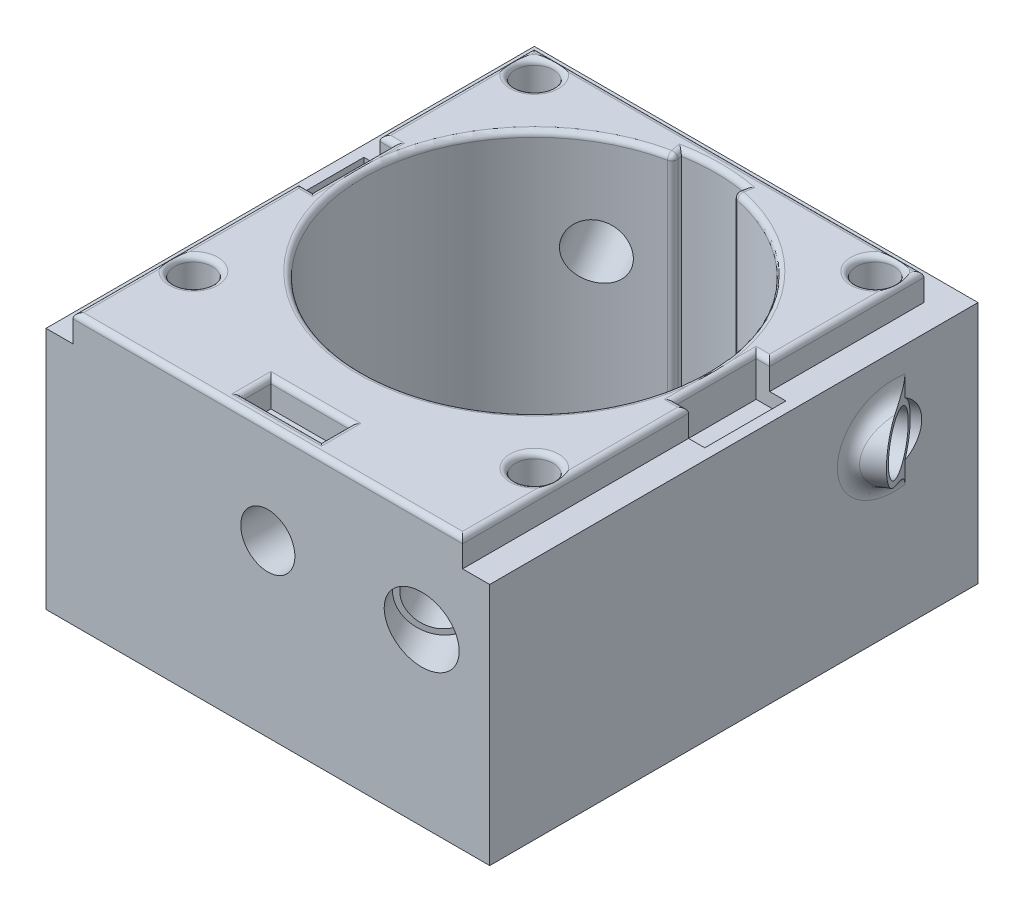
SolidWorks part; units mm, degrees
note: '?' marks a value the reader was unsure of.
ref_plane "Front Plane" through (0, 0, 0) normal (0, 0, 1) x (1, 0, 0)
ref_plane "Top Plane" through (0, 0, 0) normal (0, 1, 0) x (1, 0, 0)
ref_plane "Right Plane" through (0, 0, 0) normal (1, 0, 0) x (0, 0, -1)
sketch "Sketch1" plane through (0, 0, 0) normal (0, 1, 0) x (1, 0, 0)
  line L1 (-20.828, 22.9235) -> (20.828, 22.9235)
  line L2 (-20.828, 22.9235) -> (-20.828, -22.9235)
  line L3 (-20.828, -22.9235) -> (20.828, -22.9235)
  line L4 (20.828, 22.9235) -> (20.828, -22.9235)
  line L5 (-20.828, 22.9235) -> (20.828, -22.9235) construction
  line L6 (-20.828, -22.9235) -> (20.828, 22.9235) construction
  point P0 (0, 0)
  dimension "D1" = 45.847
  dimension "D2" = 41.656
extrude "Boss-Extrude1" add sketch "Sketch1" along normal blind 25.4 contours L2 L1 L4 L3
sketch "Sketch2" plane through (0, 25.4, 0) normal (0, 1, 0) x (1, 0, 0)
  line L0 (0, 22.9235) -> (0, 2.0955) construction
  line L1 (-20.828, 22.9235) -> (20.828, 22.9235) construction
  circle A0 centre (0, 2.0955) radius 16.129
  dimension "D2" = 32.258
  dimension "D1" = 20.828
ref_axis "Axis1" through (0, 25.4, -2.0955) along (0, 1, 0)?
sketch "Sketch7" plane through (0, 0, 22.9235) normal (0, 0, 1) x (1, 0, 0)
  line L0 (0, 0) -> (0, 16.002) construction
  line L1 (-20.828, 0) -> (20.828, 0) construction
  circle A0 centre (0, 16.002) radius 3.048
  dimension "D2" = 6.096
  dimension "D1" = 16.002
extrude "Boss-Extrude5" add sketch "Sketch7" along normal blind 23.114 separate body
sketch "Sketch25" plane through (0, 0, 22.9235) normal (0, 0, -1) x (-1, 0, 0)
  circle A0 centre (0, 16.002) radius 3.048 construction
  circle A1 centre (0, 16.002) radius 3.048 construction
  circle A2 centre (0, 16.002) radius 2.54
  dimension "D1" = 0.508
extrude "Boss-Extrude6" add sketch "Sketch25" along normal blind 14.478
pattern_circular "CirPattern2" count 2 every 120 about axis through (0, 25.4, -2.0955) along (0, 1, 0) of bodies 125
pattern_circular "CirPattern3" count 2 over 360 about axis through (0, 25.4, -2.0955) along (0, 1, 0)
pattern_circular "CirPattern4" count 2 every 30 about axis through (0, 25.4, -2.0955) along (0, 1, 0) of bodies 125
combine bodies "Combine1" bodies to combine 101 125 129 127 128
sketch "Sketch30" plane through (22.5745, 0, -13.0334) normal (0.866, 0, -0.5) x (-0.5, 0, -0.866)
  line L2 (3.4929, 18.5464) -> (3.4929, 17.9087)
  line L3 (3.4929, 14.0953) -> (3.4929, 13.4576)
  line L4 (3.4929, 18.5464) -> (3.4929, 17.9087) construction
  line L5 (3.4929, 14.0953) -> (3.4929, 13.4576) construction
  circle A0 centre (1.8148, 16.002) radius 2.54
  circle A1 centre (1.8148, 16.002) radius 3.048
  arc A2 (3.4929, 13.4576) -> (3.4929, 18.5464) centre (1.8148, 16.002) ccw
  arc A3 (3.4929, 14.0953) -> (3.4929, 17.9087) centre (1.8148, 16.002) ccw
  arc A4 (3.4929, 13.4576) -> (3.4929, 18.5464) centre (1.8148, 16.002) ccw construction
  arc A5 (3.4929, 14.0953) -> (3.4929, 17.9087) centre (1.8148, 16.002) ccw construction
  point P5 (0, 0)
  dimension "D1" = 0
extrude "Boss-Extrude8" add sketch "Sketch30" against normal blind 3.81 contours A1 | A0
sketch "Sketch31" plane through (-13.4169, 0, -23.2387) normal (-0.5, 0, -0.866) x (-0.866, 0, 0.5)
  circle A0 centre (-1.0478, 16.002) radius 2.54 construction
  circle A1 centre (-1.0478, 16.002) radius 2.54
  circle A2 centre (-1.0478, 16.002) radius 3.048
extrude "Boss-Extrude9" add sketch "Sketch31" against normal blind 3.302
extrude "Cut-Extrude1" cut sketch "Sketch2" against normal up to surface (25.4 mm away) up to face at (0, 0, 0)
sketch "Sketch3" plane through (0, 25.4, 0) normal (0, 1, 0) x (1, 0, 0)
  line L0 (-18.415, 2.0955) -> (18.415, 2.0955) construction
  line L1 (0, 2.0955) -> (0, -22.9235) construction
  line L2 (17.018, -1.7145) -> (19.812, -1.7145)
  line L3 (17.018, -1.7145) -> (17.018, 5.9055)
  line L4 (17.018, 5.9055) -> (19.812, 5.9055)
  line L5 (19.812, -1.7145) -> (19.812, 5.9055)
  line L6 (17.018, -1.7145) -> (19.812, 5.9055) construction
  line L7 (17.018, 5.9055) -> (19.812, -1.7145) construction
  line L9 (-17.018, 5.9055) -> (-19.812, -1.7145) construction
  line L10 (-17.018, -1.7145) -> (-19.812, 5.9055) construction
  line L11 (-19.812, -1.7145) -> (-19.812, 5.9055)
  line L12 (-17.018, 5.9055) -> (-19.812, 5.9055)
  line L13 (-17.018, -1.7145) -> (-17.018, 5.9055)
  line L14 (-17.018, -1.7145) -> (-19.812, -1.7145)
  point P14 (0, 2.0955)
  dimension "D1" = 18.415
  dimension "D2" = 7.62
  dimension "D3" = 2.794
extrude "Cut-Extrude2" cut sketch "Sketch3" against normal blind 3.81
sketch "Sketch6" plane through (0, 25.4, 0) normal (0, 1, 0) x (1, 0, 0)
  line L0 (0, 2.0955) -> (0, 18.2245) construction
  line L1 (0, 2.0955) -> (-2.9551, 18.855)
  line L2 (0, 2.0955) -> (2.9551, 18.855)
  circle A0 centre (0, 2.0955) radius 17.018
  circle A1 centre (0, 2.0955) radius 16.129 construction
  circle M16 centre (0, 2.0955) radius 16.129
  dimension "D1" = 34.036
  dimension "D2" = 10
extrude "Cut-Extrude6" cut sketch "Sketch6" against normal up to surface (25.4 mm away) contours L2 A0 L1 M16 | L0 L2 M16 | L1 L0 M16
sketch "Sketch14" plane through (0, 25.4, 0) normal (0, 1, 0) x (1, 0, 0)
  line L0 (20.828, 22.9235) -> (20.828, -22.9235) construction
  line L1 (-20.828, 22.9235) -> (20.828, 22.9235)
  line L2 (-20.828, 22.9235) -> (-20.828, 20.3835)
  line L3 (-20.828, 20.3835) -> (20.828, 20.3835)
  line L4 (20.828, 22.9235) -> (20.828, 20.3835)
  line L5 (-20.828, -22.9235) -> (20.828, -22.9235) construction
  line L6 (20.828, -22.9235) -> (18.288, -22.9235)
  line L7 (20.828, -22.9235) -> (20.828, 20.3835)
  line L8 (20.828, 20.3835) -> (18.288, 20.3835)
  line L9 (18.288, -22.9235) -> (18.288, 20.3835)
  line L10 (-20.828, 20.3835) -> (-18.3034, 20.3835)
  line L11 (-20.828, 20.3835) -> (-20.828, -22.9235)
  line L12 (-20.828, -22.9235) -> (-18.3034, -22.9235)
  line L13 (-18.3034, 20.3835) -> (-18.3034, -22.9235)
  line L15 (-3.7183, -18.9209) -> (3.7183, -18.9209)
  line L16 (-3.7183, -18.9209) -> (-3.7183, -21.5937)
  line L17 (-3.7183, -21.5937) -> (3.7183, -21.5937)
  line L18 (3.7183, -18.9209) -> (3.7183, -21.5937)
  line L19 (-3.7183, -18.9209) -> (3.7183, -21.5937) construction
  line L20 (-3.7183, -21.5937) -> (3.7183, -18.9209) construction
  point P16 (0, -20.2573)
  line M7 (-20.828, -22.9235) -> (20.828, -22.9235)
  line M8 (20.828, -22.9235) -> (20.828, 22.9235)
  line M9 (20.828, 22.9235) -> (-20.828, 22.9235)
  line M10 (-20.828, 22.9235) -> (-20.828, -22.9235)
  line M15 (17.018, 5.9055) -> (19.812, 5.9055)
  line M16 (19.812, 5.9055) -> (19.812, -1.7145)
  line M17 (19.812, -1.7145) -> (17.018, -1.7145)
  dimension "D1" = 2.54
  dimension "D2" = 2.54
  dimension "D3" = 2.5246
extrude "Cut-Extrude10" cut sketch "Sketch14" against normal blind 2.54 contours L18 L15 L16 L17 | L9 L3 M7 M8 M15 M16 M17 | L3 M10 M8 M9 | L11 L12 L13 L10
sketch "Sketch4" plane through (0, 25.4, 0) normal (0, 1, 0) x (1, 0, 0)
  line L0 (0, 2.0955) -> (0, 22.9235) construction
  line L2 (0, 2.0955) -> (-11.5271, 2.0955) construction
  line L3 (-16.002, -13.9065) -> (16.002, -13.9065) construction
  line L4 (-16.002, -13.9065) -> (-16.002, 18.0975) construction
  line L5 (-16.002, 18.0975) -> (16.002, 18.0975) construction
  line L6 (16.002, -13.9065) -> (16.002, 18.0975) construction
  line L7 (-16.002, -13.9065) -> (16.002, 18.0975) construction
  line L8 (-16.002, 18.0975) -> (16.002, -13.9065) construction
  circle A0 centre (-16.002, -13.9065) radius 1.778
  circle A1 centre (-16.002, 18.0975) radius 1.778
  circle A2 centre (16.002, 18.0975) radius 1.778
  circle A3 centre (16.002, -13.9065) radius 1.778
  point P2 (0, 2.0955)
  dimension "D3" = 3.556
  dimension "D1" = 32.004
  dimension "D2" = 32.004
extrude "Cut-Extrude14" cut sketch "Sketch4" against normal through all
fillet "Fillet1" radius 0.508 26 edges at (2.8008, 12.7, -17.9795) (-2.8008, 12.7, -17.9795) (-0.0077, 25.4, 22.9235) (-18.3034, 25.4, 12.319) (-17.6607, 25.4, 1.7145) (-17.018, 25.4, -2.0955) (-17.6607, 25.4, -5.9055) (-18.3034, 25.4, -13.1445) (-0.0077, 25.4, -20.3835) (18.288, 25.4, -13.1445) (17.653, 25.4, -5.9055) (17.018, 25.4, -2.0955) (17.653, 25.4, 1.7145) (18.288, 25.4, 12.319) (0, 25.4, 14.0335) (2.878, 25.4, -18.4172) (0, 25.4, -19.1135) (-2.878, 25.4, -18.4172) (0, 25.4, 18.9209) (-3.7183, 25.4, 20.2573) (0, 25.4, 21.5937) (3.7183, 25.4, 20.2573) (-16.002, 25.4, 15.6845) (-16.002, 25.4, -19.8755) (16.002, 25.4, -16.3195) (16.002, 25.4, 12.1285)
fillet "Fillet9" radius 1.524 2 edges at (20.828, 16.002, -10.601) (-8.5055, 16.002, -22.9235)
